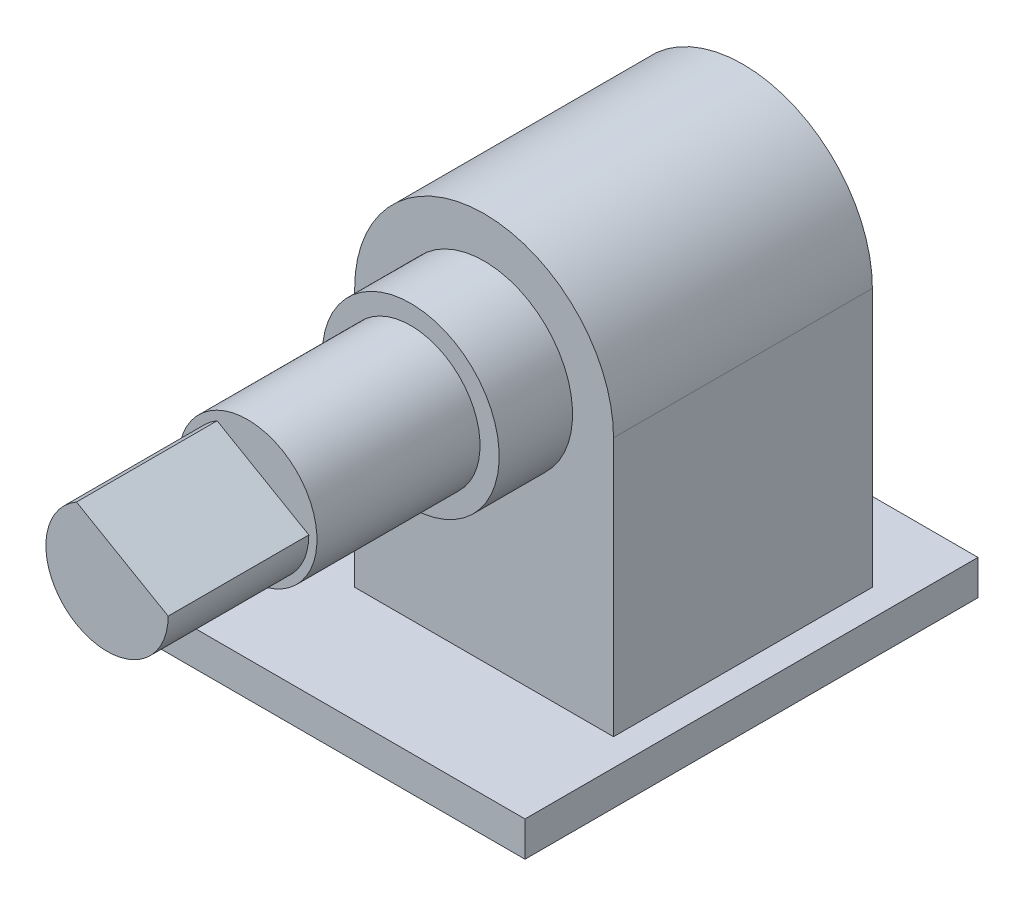
SolidWorks part; units mm, degrees
ref_plane "Front Plane" through (0, 0, 0) normal (0, 0, 1) x (1, 0, 0)
ref_plane "Top Plane" through (0, 0, 0) normal (0, 1, 0) x (1, 0, 0)
ref_plane "Right Plane" through (0, 0, 0) normal (1, 0, 0) x (0, 0, -1)
sketch "Sketch1" plane through (0, 0, 0) normal (0, 1, 0) x (1, 0, 0)
  line L1 (9.652, 11.1125) -> (-9.652, 11.1125)
  line L2 (9.652, 11.1125) -> (9.652, -11.1125)
  line L3 (9.652, -11.1125) -> (-9.652, -11.1125)
  line L4 (-9.652, 11.1125) -> (-9.652, -11.1125)
  line L5 (0, -11.1125) -> (0, 11.1125) construction
  line L6 (9.652, 0) -> (-9.652, 0) construction
  point P0 (0, 0)
  dimension "D1" = 22.225
  dimension "D2" = 19.304
extrude "Boss-Extrude1" add sketch "Sketch1" along normal blind 1.7145
sketch "Sketch2" plane through (0, 1.7145, 0) normal (0, 1, 0) x (1, 0, 0)
  line L0 (9.652, -11.1125) -> (9.652, 11.1125) construction
  line L1 (-4.3688, -5.4483) -> (8.3312, -5.4483)
  line L2 (-4.3688, -5.4483) -> (-4.3688, 7.2517)
  line L3 (-4.3688, 7.2517) -> (8.3312, 7.2517)
  line L4 (8.3312, -5.4483) -> (8.3312, 7.2517)
  line L5 (-4.3688, -5.4483) -> (8.3312, 7.2517) construction
  line L6 (-4.3688, 7.2517) -> (8.3312, -5.4483) construction
  line L7 (9.652, 11.1125) -> (-9.652, 11.1125) construction
  point P4 (1.9812, 0.9017)
  dimension "D1" = 12.7
  dimension "D2" = 12.7
  dimension "D3" = 1.3208
  dimension "D4" = 3.8608
extrude "Boss-Extrude2" add sketch "Sketch2" along normal blind 19.05
fillet "Fillet1" 2 edges at (8.3312, 20.7645, -0.9017) (-4.3688, 20.7645, -0.9017) type full round first side face at (8.3312, 11.2395, -0.9017) second side face at (-4.3688, 11.2395, -0.9017) middle face at (1.9812, 20.7645, -0.9017)
ref_plane "Plane1" through (0, 14.4145, 0) normal (0, 1, 0) x (1, 0, 0)
sketch "Sketch6" plane through (0, 14.4145, 0) normal (0, 1, 0) x (1, 0, 0)
  line L0 (1.9812, -5.4483) -> (1.9812, -23.9483) construction
  line L1 (-4.3688, -5.4483) -> (8.3312, -5.4483) construction
  line L2 (1.9812, -23.9483) -> (-1.0188, -23.9483)
  line L3 (-1.0188, -23.9483) -> (-1.0188, -17.0483)
  line L4 (-1.0188, -17.0483) -> (-1.4188, -17.0483)
  line L5 (-1.4188, -17.0483) -> (-1.4188, -9.0483)
  line L6 (-1.4188, -9.0483) -> (-2.3588, -9.0483)
  line L7 (-2.3588, -9.0483) -> (-2.3588, -5.4483)
  line L8 (-2.3588, -5.4483) -> (1.9812, -5.4483)
  line L9 (1.9812, -5.4483) -> (1.9812, -23.9483)
  dimension "D1" = 6
  dimension "D2" = 6.8
  dimension "D3" = 8.68
  dimension "D4" = 3.6
  dimension "D5" = 8
  dimension "D6" = 6.9
revolve "Revolve1" add sketch "Sketch6" angle 360 about L0
sketch "Sketch7" plane through (0, 0, 23.9483) normal (0, 0, 1) x (1, 0, 0)
  line L0 (0.4812, 17.0126) -> (4.9812, 14.4145)
  line L1 (2.7312, 15.7135) -> (0.4812, 11.8164) construction
  circle A2 centre (1.9812, 14.4145) radius 3 construction
  circle A3 centre (1.9812, 14.4145) radius 3 construction
  arc A4 (4.9812, 14.4145) -> (0.4812, 17.0126) centre (1.9812, 14.4145) ccw
  point P4 (0.4817, 11.8162)
  point P8 (2.4334, 15.1977)
  point P9 (0.9265, 11.606)
  dimension "D1" = 30
  dimension "D2" = 4.5
extrude "Cut-Extrude1" cut sketch "Sketch7" against normal up to surface (6.9 mm away) up to face at (-1.0188, 14.4145, 17.0483)
